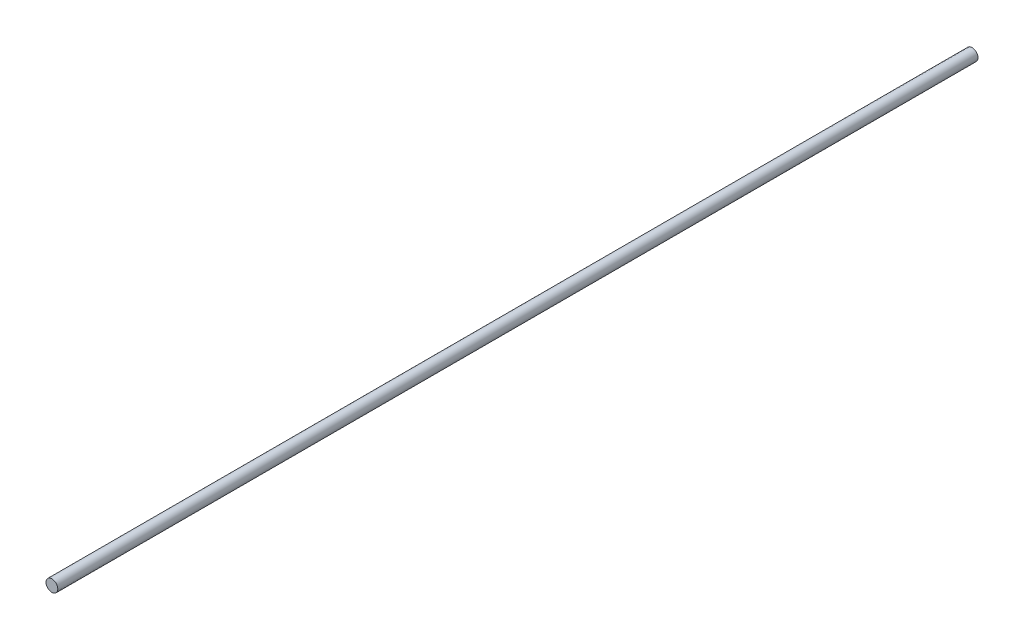
SolidWorks part; units mm, degrees
ref_plane "Front Plane" through (0, 0, 0) normal (0, 0, 1) x (1, 0, 0)
ref_plane "Top Plane" through (0, 0, 0) normal (0, 1, 0) x (1, 0, 0)
ref_plane "Right Plane" through (0, 0, 0) normal (1, 0, 0) x (0, 0, -1)
sketch "Sketch1" plane through (0, 0, 0) normal (0, 0, 1) x (1, 0, 0)
  circle A0 centre (-6.8053, 9.037) radius 1.5875
  dimension "D1" = 3.175
extrude "Boss-Extrude1" add sketch "Sketch1" along normal blind 247.65
